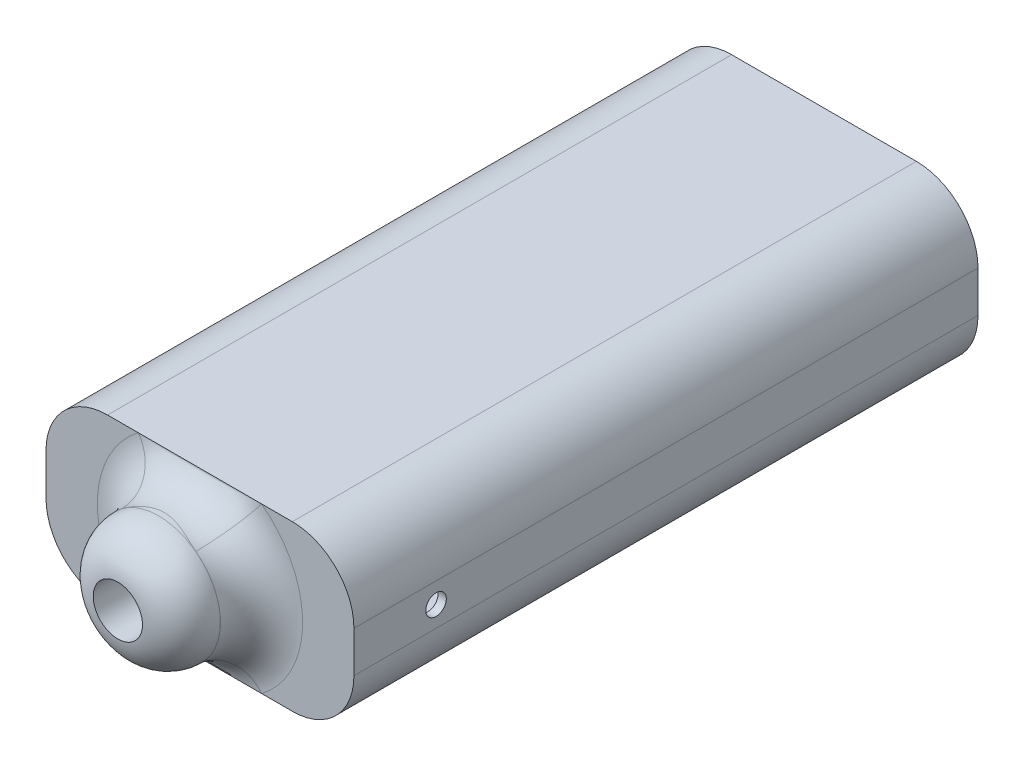
SolidWorks part; units mm, degrees
material "PLA Aero Bambu"
ref_plane "Front Plane" through (0, 0, 0) normal (0, 0, 1) x (1, 0, 0)
ref_plane "Top Plane" through (0, 0, 0) normal (0, 1, 0) x (1, 0, 0)
ref_plane "Right Plane" through (0, 0, 0) normal (1, 0, 0) x (0, 0, -1)
sketch "Sketch1" plane through (0, 0, 0) normal (0, 0, 1) x (1, 0, 0)
  line L1 (-18.75, 10) -> (18.75, 10)
  line L2 (-18.75, 10) -> (-18.75, -10)
  line L3 (-18.75, -10) -> (18.75, -10)
  line L4 (18.75, 10) -> (18.75, -10)
  line L5 (-18.75, 10) -> (18.75, -10) construction
  line L6 (-18.75, -10) -> (18.75, 10) construction
  circle A0 centre (0, 0) radius 2
  point P0 (0, 0)
  dimension "D3" = 4
  dimension "D1" = 20
  dimension "D2" = 37.5
extrude "Boss-Extrude1" add sketch "Sketch1" against normal blind 1
sketch "Sketch2" plane through (0, 0, -1) normal (0, 0, -1) x (-1, 0, 0)
  line L0 (-18.75, 10) -> (-18.75, -10)
  line L1 (18.75, -10) -> (-18.75, -10) construction
  line L2 (-18.75, -10) -> (18.75, -10)
  line L3 (18.75, -10) -> (18.75, 10)
  line L4 (18.75, 10) -> (-18.75, 10)
  line L5 (17.75, 9) -> (-17.75, 9)
  line L6 (-17.75, 9) -> (-17.75, -9)
  line L7 (-17.75, -9) -> (17.75, -9)
  line L8 (17.75, -9) -> (17.75, 9)
  dimension "D1" = 1
extrude "Boss-Extrude2" add sketch "Sketch2" along normal blind 75
fillet "Fillet2" radius 7.5 8 edges at (18.75, 10, -38) (18.75, -10, -38) (-18.75, -10, -38) (-18.75, 10, -38) (-17.75, -9, -38.5) (-17.75, 9, -38.5) (17.75, 9, -38.5) (17.75, -9, -38.5)
sketch "Sketch4" plane through (0, 0, 0) normal (0, 0, 1) x (1, 0, 0)
  circle A0 centre (0, 0) radius 7.5
  circle A1 centre (0, 0) radius 3
  dimension "D1" = 6
  dimension "D2" = 15
extrude "Boss-Extrude3" add sketch "Sketch4" along normal blind 10
fillet "Fillet3" radius 5 2 edges at (7.5, 0, 0) (7.5, 0, 10)
sketch "Sketch5" plane through (18.75, 0, 0) normal (1, 0, 0) x (0, 0, -1)
  circle A0 centre (10, 0) radius 1.25
  dimension "D1" = 2.5
  dimension "D2" = 10
extrude "Cut-Extrude1" cut sketch "Sketch5" against normal through all
